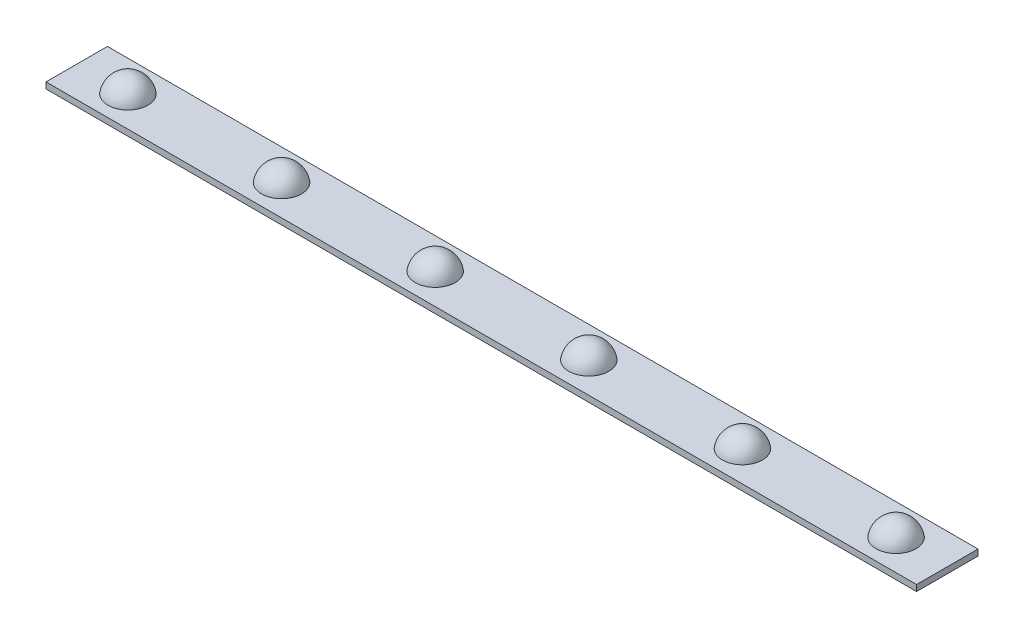
SolidWorks part; units mm, degrees
ref_plane "Front" through (0, 0, 0) normal (0, 0, 1) x (1, 0, 0)
ref_plane "Top" through (0, 0, 0) normal (0, 1, 0) x (1, 0, 0)
ref_plane "Right" through (0, 0, 0) normal (1, 0, 0) x (0, 0, -1)
sketch "Sketch1" plane through (0, 0, 0) normal (1, 0, 0) x (0, 0, -1)
  line L1 (5.6388, 0) -> (-5.6388, 0) construction
  line L4 (-4.1393, 22.8203) -> (-0.7433, 22.6989)
  line L5 (-1.1312, 21.5182) -> (-4.1819, 21.6273)
  line L6 (-4.445, 18.415) -> (-5.6388, 18.415)
  line L7 (-4.445, 21.3734) -> (-4.445, 18.415)
  line L8 (-5.6388, 18.415) -> (-5.6388, 21.3734)
  line L9 (3.9237, 21.6269) -> (0.7619, 21.5441)
  line L10 (5.6388, 0) -> (5.6388, 21.1191)
  line L11 (4.445, 21.1191) -> (4.445, 0)
  line L12 (5.6388, 0) -> (4.445, 0)
  line L13 (-0.7433, 22.6989) -> (3.8925, 22.8203)
  arc A0 (-4.445, 21.3734) -> (-4.1819, 21.6273) centre (-4.191, 21.3734) cw
  arc A1 (-5.6388, 21.3734) -> (-4.1393, 22.8203) centre (-4.191, 21.3734) cw
  arc A3 (3.9237, 21.6269) -> (4.445, 21.1191) centre (3.937, 21.1191) cw
  arc A4 (3.8925, 22.8203) -> (5.6388, 21.1191) centre (3.937, 21.1191) cw
  arc A5 (-1.1312, 21.5182) -> (0.7619, 21.5441) centre (-0.1524, 19.1744) cw
  dimension "D2" = 19.1744
  dimension "D7" = 0.254
  dimension "D8" = 0.508
  dimension "D6" = 2.54
  dimension "D9" = 1.1938
  dimension "D10" = 88.5
  dimension "D1" = 11.2776
  dimension "D3" = 5.7912
  dimension "D4" = 36.83
  dimension "D5" = 1.1938
  dimension "D11" = 87.953
  dimension "D12" = 45.6406
extrude "Extrude1" add sketch "Sketch1" along normal mid plane 400.05
ref_plane "Travel / 2" through (-403.225, 0, 0) normal (-1, 0, 0) x (0, 0, 1)
sketch "Sketch2" plane through (-403.225, 0, 0) normal (-1, 0, 0) x (0, 0, 1)
  line L0 (0.0254, 6.1159) -> (0.0254, 0)
  line L2 (-5.6388, 0) -> (5.6388, 0) construction
  line L3 (5.6388, 21.3734) -> (5.6388, 18.415) construction
  line L7 (-4.445, 21.1191) -> (-4.445, 0) construction
  line L8 (-5.6388, 0) -> (-5.6388, 21.1191) construction
  line L13 (-3.5306, 16.3766) -> (-3.5306, 9.5217)
  line L46 (-2.3867, 7.7262) -> (-0.4146, 6.8065)
  arc A0 (0.0254, 6.1159) -> (-0.4146, 6.8065) centre (-0.7366, 6.1159) ccw
  arc A1 (-1.5056, 17.2916) -> (1.2415, 16.9143) centre (0.1524, 19.1744) ccw
  arc A4 (1.1312, 21.5182) -> (-0.7619, 21.5441) centre (0.1524, 19.1744) ccw construction
  arc A19 (-3.5306, 9.5217) -> (-2.3867, 7.7262) centre (-1.5494, 9.5217) ccw
  arc A25 (-1.5056, 17.2916) -> (-3.5306, 16.3766) centre (-2.3114, 16.3766) ccw
  arc A51 (5.7404, 15.6277) -> (1.2415, 16.9143) centre (2.7686, 13.7451) ccw
  dimension "D2" = 8.4074
  dimension "D3" = 27.4903
  dimension "D6" = 1.9812
  dimension "D8" = 12.2319
  dimension "D10" = 2.5088
  dimension "D11" = 1.2192
  dimension "D4" = 0.762
  dimension "D5" = 4.4704
  dimension "D7" = 115
  dimension "D9" = 19.0435
  dimension "D13" = 11.3792
extrude "Middle Member" add sketch "Sketch2" against normal blind 400.05 separate body thin thin type one direction reverse wall 1.2192
ref_plane "Travel" through (-606.425, 0, 0) normal (-1, 0, 0) x (0, 0, 1)
sketch "Sketch3" plane through (-606.425, 0, 0) normal (-1, 0, 0) x (0, 0, 1)
  line L0 (1.2446, 0) -> (0.0254, 0) construction
  line L1 (-5.6388, 0) -> (-5.6388, 21.1191) construction
  line L56 (7.0612, 0) -> (7.0612, 10.6235)
  line L93 (5.5372, 12.1475) -> (5.1643, 12.1475)
  arc A0 (1.2082, 11.9072) -> (4.2365, 11.8325) centre (2.7686, 13.7451) ccw
  arc A29 (7.0612, 10.6235) -> (5.5372, 12.1475) centre (5.5372, 10.6235) ccw
  arc A53 (5.1643, 12.1475) -> (4.2365, 11.8325) centre (5.1643, 10.6235) ccw
  dimension "D1" = 1.524
  dimension "D4" = 1.524
  dimension "D5" = 2.411
  dimension "D2" = 12.7
  dimension "D3" = 12.1475
  dimension "D6" = 5.853
extrude "Drawer Member" add sketch "Sketch3" against normal blind 400.05 thin thin type one direction wall 1.397
sketch "Sketch6" plane through (0, 0, 7.0612) normal (0, 0, 1) x (1, 0, 0)
  line L1 (-606.425, 0) -> (-604.52, 0)
  line L2 (-606.425, 0) -> (-606.425, 12.1475)
  line L3 (-606.425, 12.1475) -> (-604.52, 12.1475)
  line L4 (-604.52, 0) -> (-604.52, 12.1475)
  line L5 (-206.375, 12.1475) -> (-606.425, 12.1475) construction
  line L7 (-606.425, 10.6235) -> (-606.425, 0) construction
  line L8 (-206.375, 0) -> (-606.425, 0) construction
  dimension "D1" = 1.905
extrude "Cut-Extrude1" cut sketch "Sketch6" against normal through all
sketch "Sketch8" plane through (0, 0, -4.445) normal (0, 0, 1) x (1, 0, 0)
  line L0 (190.3865, 7.6456) -> (191.8208, 7.493)
  line L1 (200.025, 12.2048) -> (190.6284, 12.2048)
  line L2 (191.8208, 7.493) -> (191.8208, 0)
  line L3 (200.025, 0) -> (-200.025, 0) construction
  line L4 (200.025, 21.1191) -> (200.025, 0) construction
  line L5 (200.025, 12.2048) -> (200.025, 0)
  line L6 (200.025, 0) -> (191.8208, 0)
  arc A0 (190.6284, 12.2048) -> (190.3865, 7.6456) centre (190.6284, 9.9188) ccw
  dimension "D3" = 9.9188
  dimension "D1" = 12.2048
  dimension "D2" = 8.2042
  dimension "D4" = 9.3966
  dimension "D5" = 7.493
extrude "Cut-Extrude2" cut sketch "Sketch8" against normal up to next (1.1938 mm away)
sketch "Sketch11" plane through (0, 0, 7.0612) normal (0, 0, 1) x (1, 0, 0)
  line L0 (-212.09, 5.9678) -> (-212.09, 0)
  line L8 (-206.375, 8.5893) -> (-212.2343, 7.2212)
  line L11 (-212.09, 0) -> (-206.375, 0)
  line L12 (-206.375, 0) -> (-206.375, 8.5893)
  arc A1 (-212.2343, 7.2212) -> (-212.09, 5.9678) centre (-212.0899, 6.6028) ccw
  dimension "D3" = 0.635
  dimension "D1" = 5.715
  dimension "D2" = 8.5893
  dimension "D4" = 5.9678
  dimension "D5" = 103.143
extrude "Cut-Extrude3" cut sketch "Sketch11" against normal up to next (1.397 mm away)
sketch "Sketch12" plane through (0, 0, 1.2446) normal (0, 0, 1) x (1, 0, 0)
  line L0 (-3.175, 12.065) -> (-13.335, 12.065)
  line L1 (-3.175, 16.3766) -> (-3.175, 9.5217) construction
  line L2 (-15.875, 9.525) -> (-15.875, 0)
  line L3 (-3.175, 0) -> (-403.225, 0) construction
  line L4 (-15.875, 0) -> (-3.175, 0)
  line L5 (-3.175, 0) -> (-3.175, 12.065)
  arc A0 (-13.335, 12.065) -> (-15.875, 9.525) centre (-13.335, 9.525) ccw
  point P11 (-15.875, 12.065)
  dimension "D3" = 2.54
  dimension "D1" = 12.7
  dimension "D2" = 12.065
extrude "Cut-Extrude4" cut sketch "Sketch12" against normal through all
sketch "Sketch13" plane through (0, 0, -4.445) normal (0, 0, 1) x (1, 0, 0)
  line L0 (-131.6367, 7.112) -> (-156.4652, 7.112)
  line L1 (191.8208, 0) -> (-200.025, 0) construction
  line L2 (-139.7266, 0) -> (-139.7266, 4.2392) construction
  line L3 (-182.5637, 10.287) -> (-131.6367, 10.287)
  line L4 (-200.025, 21.1191) -> (-200.025, 0) construction
  line L5 (-160.2752, 7.112) -> (-182.5637, 7.112)
  line L6 (-159.5132, 0) -> (-159.5132, 6.35)
  line L7 (-157.2272, 6.35) -> (-157.2272, 0)
  line L8 (-137.2501, 2.286) -> (-142.2031, 2.286)
  line L13 (-176.3026, 0) -> (-171.7306, 0)
  line L14 (-168.2, 0) -> (-161.85, 0)
  line L15 (-159.5132, 0) -> (-157.2272, 0)
  line L16 (-154.7126, 0) -> (-150.1406, 0)
  line L17 (-144.4891, 0) -> (-134.9641, 0)
  arc A1 (-182.5637, 10.287) -> (-182.5637, 7.112) centre (-182.5637, 8.6995) ccw
  arc A2 (-159.5132, 6.35) -> (-160.2752, 7.112) centre (-160.2752, 6.35) ccw
  arc A4 (-156.4652, 7.112) -> (-157.2272, 6.35) centre (-156.4652, 6.35) ccw
  arc A7 (-131.6367, 7.112) -> (-131.6367, 10.287) centre (-131.6367, 8.6995) ccw
  arc A8 (-161.85, 0) -> (-168.2, 0) centre (-165.025, 0) ccw
  arc A9 (-171.7306, 0) -> (-176.3026, 0) centre (-174.0166, 0) ccw
  arc A10 (-150.1406, 0) -> (-154.7126, 0) centre (-152.4266, 0) ccw
  arc A11 (-134.9641, 0) -> (-137.2501, 2.286) centre (-137.2501, 0) ccw
  arc A12 (-142.2031, 2.286) -> (-144.4891, 0) centre (-142.2031, 0) ccw
  dimension "D3" = 2.286
  dimension "D4" = 3.175
  dimension "D7" = 8.9916
  dimension "D8" = 21.59
  dimension "D9" = 34.29
  dimension "D10" = 0.762
  dimension "D11" = 17.5387
  dimension "D12" = 9.525
  dimension "D13" = 5.5118
  dimension "D14" = 35
  dimension "D1" = 3.175
  dimension "D2" = 50.927
  dimension "D5" = 2.286
  dimension "D6" = 10.287
extrude "Cut-Extrude5" cut sketch "Sketch13" against normal up to next (1.1938 mm away)
sketch "Sketch32" plane through (0, 0, -5.6388) normal (0, 0, -1) x (-1, 0, 0)
  line L0 (19.5625, 0) -> (29.0875, 0)
  line L1 (33.85, 0) -> (40.2, 0)
  line L2 (43.6925, 0) -> (53.2175, 0)
  line L3 (56.583, 0) -> (61.155, 0)
  line L4 (-191.8208, 0) -> (134.9641, 0) construction
  line L5 (182.5637, 10.287) -> (131.6367, 10.287) construction
  line L6 (131.6367, 7.112) -> (156.4652, 7.112) construction
  line L7 (48.455, 2.286) -> (48.455, -3.4269) construction
  line L8 (24.325, 2.286) -> (24.325, -3.4269) construction
  line L14 (16.3875, 10.287) -> (59.631, 10.287)
  line L15 (55.059, 7.112) -> (16.3875, 7.112)
  line L17 (61.155, 8.763) -> (61.155, 0)
  line L18 (56.583, 0) -> (56.583, 5.588)
  line L23 (21.8485, 2.286) -> (26.8015, 2.286)
  line L25 (45.9785, 2.286) -> (50.9315, 2.286)
  arc A0 (168.2, 0) -> (161.85, 0) centre (165.025, 0) ccw construction
  arc A13 (61.155, 8.763) -> (59.631, 10.287) centre (59.631, 8.763) ccw
  arc A14 (56.583, 5.588) -> (55.059, 7.112) centre (55.059, 5.588) ccw
  arc A17 (16.3875, 10.287) -> (16.3875, 7.112) centre (16.3875, 8.6995) ccw
  arc A20 (29.0875, 0) -> (26.8015, 2.286) centre (26.8015, 0) ccw
  arc A21 (21.8485, 2.286) -> (19.5625, 0) centre (21.8485, 0) ccw
  arc A22 (40.2, 0) -> (33.85, 0) centre (37.025, 0) ccw
  arc A24 (53.2175, 0) -> (50.9315, 2.286) centre (50.9315, 0) ccw
  arc A25 (45.9785, 2.286) -> (43.6925, 0) centre (45.9785, 0) ccw
  dimension "D2" = 1.524
  dimension "D3" = 3.175
  dimension "D4" = 9.525
  dimension "D5" = 2.286
  dimension "D6" = 11.43
  dimension "D7" = 12.7
  dimension "D8" = 24.13
  dimension "D9" = 20.6375
  dimension "D10" = 128
  dimension "D1" = 4.572
extrude "Cut-Extrude14" cut sketch "Sketch32" against normal up to next (1.1938 mm away)
sketch "Sketch33" plane through (83.6094, 0.8125, -5.6388) normal (0, 0, -1) x (-1, 0, 0)
  line L0 (7.1719, -0.8125) -> (16.6969, -0.8125) construction
  line L1 (21.4594, -0.8125) -> (27.8094, -0.8125)
  line L2 (31.3019, -0.8125) -> (40.8269, -0.8125)
  line L3 (44.1924, -0.8125) -> (48.7644, -0.8125)
  line L4 (9.6484, -0.8125) -> (14.2204, -0.8125)
  line L7 (36.0644, 1.4735) -> (36.0644, -4.2394) construction
  line L8 (11.9344, 1.4735) -> (11.9344, -3.4269) construction
  line L9 (-108.2114, -0.8125) -> (103.1719, -0.8125) construction
  line L10 (143.2404, 9.4745) -> (99.9969, 9.4745) construction
  line L11 (99.9969, 6.2995) -> (138.6684, 6.2995) construction
  line L14 (3.9969, 9.4745) -> (47.2404, 9.4745)
  line L15 (42.6684, 6.2995) -> (3.9969, 6.2995)
  line L17 (48.7644, 7.9505) -> (48.7644, -0.8125)
  line L18 (44.1924, -0.8125) -> (44.1924, 4.7755)
  line L23 (9.4579, 1.4735) -> (14.4109, 1.4735) construction
  line L25 (33.5879, 1.4735) -> (38.5409, 1.4735)
  arc A0 (14.2204, -0.8125) -> (9.6484, -0.8125) centre (11.9344, -0.8125) ccw
  arc A1 (251.8094, -0.8125) -> (245.4594, -0.8125) centre (248.6344, -0.8125) ccw construction
  arc A13 (48.7644, 7.9505) -> (47.2404, 9.4745) centre (47.2404, 7.9505) ccw
  arc A14 (44.1924, 4.7755) -> (42.6684, 6.2995) centre (42.6684, 4.7755) ccw
  arc A17 (3.9969, 9.4745) -> (3.9969, 6.2995) centre (3.9969, 7.887) ccw
  arc A20 (16.6969, -0.8125) -> (14.4109, 1.4735) centre (14.4109, -0.8125) ccw construction
  arc A21 (9.4579, 1.4735) -> (7.1719, -0.8125) centre (9.4579, -0.8125) ccw construction
  arc A22 (27.8094, -0.8125) -> (21.4594, -0.8125) centre (24.6344, -0.8125) ccw
  arc A24 (40.8269, -0.8125) -> (38.5409, 1.4735) centre (38.5409, -0.8125) ccw
  arc A25 (33.5879, 1.4735) -> (31.3019, -0.8125) centre (33.5879, -0.8125) ccw
  dimension "D2" = 1.524
  dimension "D3" = 3.175
  dimension "D4" = 9.525
  dimension "D5" = 2.286
  dimension "D6" = 11.43
  dimension "D7" = 12.7
  dimension "D8" = 24.13
  dimension "D9" = 20.6375
  dimension "D10" = 224
  dimension "D1" = 4.572
extrude "Cut F" cut sketch "Sketch33" against normal up to next (1.1938 mm away)
sketch "Sketch34" plane through (169.8236, 1.4527, -5.6388) normal (0, 0, -1) x (-1, 0, 0)
  line L0 (-2.6539, -1.4527) -> (6.8711, -1.4527)
  line L1 (11.6336, -1.4527) -> (17.9836, -1.4527)
  line L2 (21.4761, -1.4527) -> (31.0011, -1.4527)
  line L3 (34.3666, -1.4527) -> (38.9386, -1.4527)
  line L4 (-21.9972, -1.4527) -> (95.8626, -1.4527) construction
  line L7 (26.2386, 0.8333) -> (26.2386, -4.8796) construction
  line L8 (2.1086, 0.8333) -> (2.1086, -4.0671) construction
  line L9 (229.4546, 8.8343) -> (186.2111, 8.8343) construction
  line L10 (186.2111, 5.6593) -> (224.8826, 5.6593) construction
  line L14 (-5.8289, 8.8343) -> (37.4146, 8.8343)
  line L15 (32.8426, 5.6593) -> (-5.8289, 5.6593)
  line L17 (38.9386, 7.3103) -> (38.9386, -1.4527)
  line L18 (34.3666, -1.4527) -> (34.3666, 4.1353)
  line L23 (-0.3679, 0.8333) -> (4.5851, 0.8333)
  line L25 (23.7621, 0.8333) -> (28.7151, 0.8333)
  arc A0 (338.0236, -1.4527) -> (331.6736, -1.4527) centre (334.8486, -1.4527) ccw construction
  arc A13 (38.9386, 7.3103) -> (37.4146, 8.8343) centre (37.4146, 7.3103) ccw
  arc A14 (34.3666, 4.1353) -> (32.8426, 5.6593) centre (32.8426, 4.1353) ccw
  arc A17 (-5.8289, 8.8343) -> (-5.8289, 5.6593) centre (-5.8289, 7.2468) ccw
  arc A20 (6.8711, -1.4527) -> (4.5851, 0.8333) centre (4.5851, -1.4527) ccw
  arc A21 (-0.3679, 0.8333) -> (-2.6539, -1.4527) centre (-0.3679, -1.4527) ccw
  arc A22 (17.9836, -1.4527) -> (11.6336, -1.4527) centre (14.8086, -1.4527) ccw
  arc A24 (31.0011, -1.4527) -> (28.7151, 0.8333) centre (28.7151, -1.4527) ccw
  arc A25 (23.7621, 0.8333) -> (21.4761, -1.4527) centre (23.7621, -1.4527) ccw
  dimension "D2" = 1.524
  dimension "D3" = 3.175
  dimension "D4" = 9.525
  dimension "D5" = 2.286
  dimension "D6" = 11.43
  dimension "D7" = 12.7
  dimension "D8" = 24.13
  dimension "D9" = 20.6375
  dimension "D10" = 320.04
  dimension "D1" = 4.572
extrude "Cut G" cut sketch "Sketch34" against normal up to next (1.1938 mm away)
sketch "Sketch31" plane through (0, 0, -5.6388) normal (0, 0, -1) x (-1, 0, 0)
  line L0 (-200.025, 12.2048) -> (-200.025, 21.1191) construction
  line L1 (-191.8208, 0) -> (-172.4775, 0) construction
  line L2 (-184.15, 0) -> (-177.8, 0)
  arc A0 (-177.8, 0) -> (-184.15, 0) centre (-180.975, 0) ccw
  dimension "D1" = 19.05
  dimension "D2" = 6.35
extrude "Cut-Extrude15" cut sketch "Sketch31" against normal up to next (1.1938 mm away)
sketch "Sketch26" plane through (0, 0, 1.2446) normal (0, 0, 1) x (1, 0, 0)
  line L0 (-176.3026, 0) -> (-134.9641, 0)
  line L1 (-171.4766, 4.826) -> (-139.7901, 4.826)
  line L2 (-19.5625, 0) -> (-53.2175, 0)
  line L3 (-48.3915, 4.826) -> (-24.3885, 4.826)
  line L4 (76.4375, 0) -> (42.7825, 0)
  line L5 (47.6085, 4.826) -> (71.6115, 4.826)
  arc A0 (-176.3026, 0) -> (-171.4766, 4.826) centre (-171.4766, 0) cw
  arc A1 (-134.9641, 0) -> (-139.7901, 4.826) centre (-139.7901, 0) ccw
  arc A2 (-53.2175, 0) -> (-48.3915, 4.826) centre (-48.3915, 0) cw
  arc A3 (-24.3885, 4.826) -> (-19.5625, 0) centre (-24.3885, 0) cw
  arc A4 (-19.5625, 0) -> (-21.8485, 2.286) centre (-21.8485, 0) ccw construction
  arc A5 (-50.9315, 2.286) -> (-53.2175, 0) centre (-50.9315, 0) ccw construction
  arc A6 (42.7825, 0) -> (47.6085, 4.826) centre (47.6085, 0) cw
  arc A7 (71.6115, 4.826) -> (76.4375, 0) centre (71.6115, 0) cw
  dimension "D1" = 4.826
extrude "Cut-Extrude17" cut sketch "Sketch26" against normal up to next (1.2192 mm away)
ref_plane "Plane3" through (-187.325, 0, 0) normal (-1, 0, 0) x (0, 0, 1)
sketch "Sketch27" plane through (-187.325, 0, 0) normal (-1, 0, 0) x (0, 0, 1)
  line L0 (0.1524, 21.6832) -> (0.1524, 16.6656)
  line L1 (0.1524, 23.635) -> (0.1524, 15.2838) construction
  arc A0 (0.1524, 16.6656) -> (0.1524, 21.6832) centre (0.1524, 19.1744) ccw
  arc A1 (-1.5056, 17.2916) -> (1.2415, 16.9143) centre (0.1524, 19.1744) ccw construction
revolve "Revolve1" add sketch "Sketch27" angle 360 about L1
pattern_linear "LPattern1" count 6 spacing 19.05 along (1, 0, 0) of bodies 128
sketch "Sketch28" plane through (-187.325, 0, 0) normal (-1, 0, 0) x (0, 0, 1)
  line L0 (2.6612, 19.1744) -> (-2.3564, 19.1744) construction
  line L1 (3.9624, 18.7934) -> (-3.6576, 18.7934)
  line L2 (3.9624, 18.7934) -> (3.9624, 19.5554)
  line L3 (3.9624, 19.5554) -> (-3.6576, 19.5554)
  line L4 (-3.6576, 18.7934) -> (-3.6576, 19.5554)
  line L5 (0.1524, 20.5465) -> (0.1524, 17.804) construction
  circle A1 centre (0.1524, 19.1744) radius 2.5088 construction
  point P8 (0.1524, 19.1744)
  dimension "D1" = 7.62
  dimension "D2" = 0.762
extrude "Extrude7" add sketch "Sketch28" along normal blind 6.35 and the other way blind 101.6
ref_plane "Plane4" through (-365.125, 0, 0) normal (-1, 0, 0) x (0, 0, 1)
sketch "Sketch29" plane through (-365.125, 0, 0) normal (-1, 0, 0) x (0, 0, 1)
  line L0 (2.7686, 16.0438) -> (2.7686, 11.4464)
  line L1 (2.7686, 16.6801) -> (2.7686, 10.2973) construction
  arc A0 (2.7686, 11.4464) -> (2.7686, 16.0438) centre (2.7686, 13.7451) ccw
  arc A1 (4.7105, 14.9753) -> (1.7707, 15.816) centre (2.7686, 13.7451) ccw construction
revolve "Revolve2" add sketch "Sketch29" angle 360 about L1
pattern_linear "LPattern2" count 6 spacing 19.05 along (1, 0, 0) of bodies 135
sketch "Sketch30" plane through (-365.125, 0, 0) normal (-1, 0, 0) x (0, 0, 1)
  line L0 (0.4699, 13.7451) -> (5.0673, 13.7451) construction
  line L1 (3.9624, 18.7934) -> (3.9624, 19.5554) construction
  line L2 (0.2286, 14.1261) -> (5.3086, 14.1261)
  line L3 (0.2286, 14.1261) -> (0.2286, 13.3641)
  line L4 (0.2286, 13.3641) -> (5.3086, 13.3641)
  line L5 (5.3086, 14.1261) -> (5.3086, 13.3641)
  line L7 (2.7686, 14.2437) -> (2.7686, 12.7853) construction
  circle A0 centre (2.7686, 13.7451) radius 2.2987 construction
  point P4 (2.7686, 13.7451)
  dimension "D1" = 5.08
extrude "Extrude8" add sketch "Sketch30" along normal blind 6.35 and the other way blind 101.6
mirror "Mirror3" about plane through (0, 0, 0) normal (0, 1, 0) of bodies 118 163 159 117 124 126 127 119
mirror "Mirror5" about plane through (0, 0, 0) normal (0, 1, 0) of bodies 141 134
delete or keep bodies "Sólido-Eliminar/Conservar 1" type delete bodies bodies 150
delete or keep bodies "Sólido-Eliminar/Conservar 2" type delete bodies bodies 162
delete or keep bodies "Sólido-Eliminar/Conservar 3" type delete bodies bodies 161
delete or keep bodies "Sólido-Eliminar/Conservar 4" type delete bodies bodies 141
delete or keep bodies "Sólido-Eliminar/Conservar 5" type delete bodies bodies 152
delete or keep bodies "Sólido-Eliminar/Conservar 6" type delete bodies bodies 153
